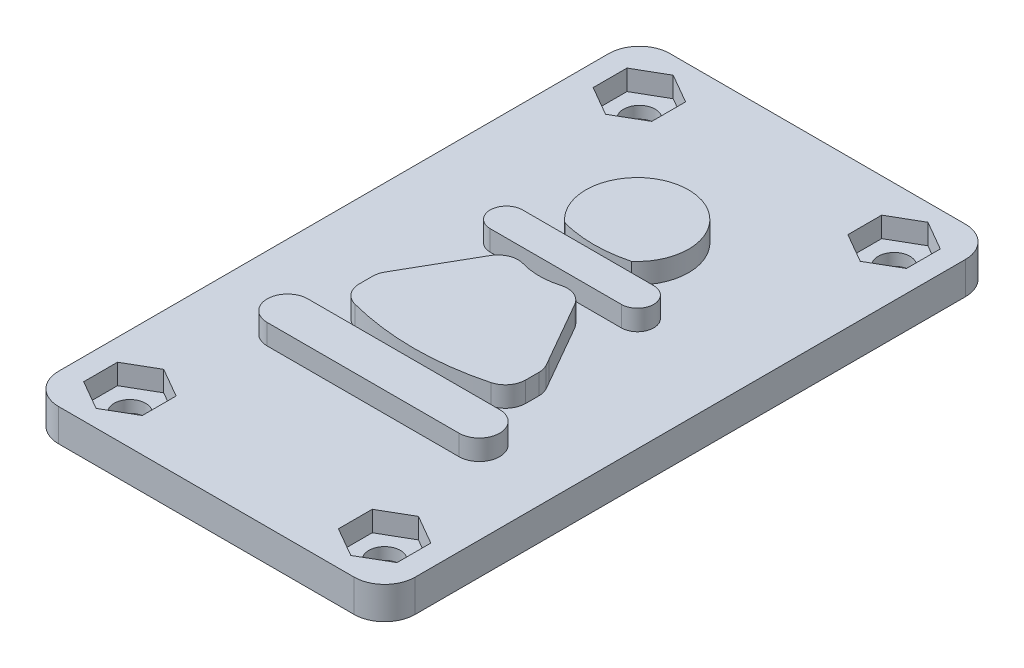
SolidWorks part; units mm, degrees
ref_plane "Front Plane" through (0, 0, 0) normal (0, 0, 1) x (1, 0, 0)
ref_plane "Top Plane" through (0, 0, 0) normal (0, 1, 0) x (1, 0, 0)
ref_plane "Right Plane" through (0, 0, 0) normal (1, 0, 0) x (0, 0, -1)
sketch "Sketch1" plane through (0, 0, 0) normal (0, 1, 0) x (1, 0, 0)
  line L1 (-12.5, -25) -> (12.5, -25) construction
  line L2 (-12.5, -25) -> (-12.5, 25) construction
  line L3 (-12.5, 25) -> (12.5, 25) construction
  line L4 (12.5, -25) -> (12.5, 25) construction
  line L5 (-12.5, -25) -> (12.5, 25) construction
  line L6 (-12.5, 25) -> (12.5, -25) construction
  line L7 (-17.5, -30) -> (17.5, -30)
  line L8 (-17.5, -30) -> (-17.5, 30)
  line L9 (-17.5, 30) -> (17.5, 30)
  line L10 (17.5, -30) -> (17.5, 30)
  line L11 (-17.5, -30) -> (17.5, 30) construction
  line L12 (-17.5, 30) -> (17.5, -30) construction
  line L13 (-12.5, 28.3198) -> (-15.375, 26.6599)
  line L14 (-15.375, 26.6599) -> (-15.375, 23.3401)
  line L15 (-15.375, 23.3401) -> (-12.5, 21.6802)
  line L16 (-12.5, 21.6802) -> (-9.625, 23.3401)
  line L17 (-9.625, 23.3401) -> (-9.625, 26.6599)
  line L18 (-9.625, 26.6599) -> (-12.5, 28.3198)
  line L19 (12.5, 28.3198) -> (9.625, 26.6599)
  line L20 (9.625, 26.6599) -> (9.625, 23.3401)
  line L21 (9.625, 23.3401) -> (12.5, 21.6802)
  line L22 (12.5, 21.6802) -> (15.375, 23.3401)
  line L23 (15.375, 23.3401) -> (15.375, 26.6599)
  line L24 (15.375, 26.6599) -> (12.5, 28.3198)
  line L25 (-12.5, -28.3198) -> (-9.625, -26.6599)
  line L26 (-9.625, -26.6599) -> (-9.625, -23.3401)
  line L27 (-9.625, -23.3401) -> (-12.5, -21.6802)
  line L28 (-12.5, -21.6802) -> (-15.375, -23.3401)
  line L29 (-15.375, -23.3401) -> (-15.375, -26.6599)
  line L30 (-15.375, -26.6599) -> (-12.5, -28.3198)
  line L31 (12.5, -21.6802) -> (9.625, -23.3401)
  line L32 (9.625, -23.3401) -> (9.625, -26.6599)
  line L33 (9.625, -26.6599) -> (12.5, -28.3198)
  line L34 (12.5, -28.3198) -> (15.375, -26.6599)
  line L35 (15.375, -26.6599) -> (15.375, -23.3401)
  line L36 (15.375, -23.3401) -> (12.5, -21.6802)
  circle A0 centre (-12.5, 25) radius 1.55
  circle A1 centre (12.5, 25) radius 1.55
  circle A2 centre (-12.5, -25) radius 1.55
  circle A3 centre (12.5, -25) radius 1.55
  circle A4 centre (-12.5, 25) radius 2.875 construction
  circle A5 centre (12.5, 25) radius 2.875 construction
  circle A6 centre (-12.5, -25) radius 2.875 construction
  circle A7 centre (12.5, -25) radius 2.875 construction
  point P0 (0, 0)
  point P10 (0, 0)
  dimension "D3" = 3.1
  dimension "D6" = 5.75
  dimension "D1" = 50
  dimension "D2" = 25
  dimension "D4" = 60
  dimension "D5" = 35
extrude "Boss-Extrude1" add sketch "Sketch1" along normal blind 3.175 contours L7 L10 L9 L8 L36 L35 L34 L33 L32 L31 L30 L29 L28 L27 L26 L25 L24 L23 L22 L21 L20 L19 L18 L17 L16 L15 L14 L13 | L17 L18 L13 L14 L15 L16 A0 | L23 L24 L19 L20 L21 L22 A1 | L35 L36 L31 L32 L33 L34 A3 | L29 L30 L25 L26 L27 L28 A2 region at (0, 0, 0) region at (-11.1064, 0, -27.4138) region at (13.8936, 0, -27.4138) region at (-13.8936, 0, 27.4138) region at (13.8936, 0, 22.5862)
extrude "Cut-Extrude1" cut sketch "Sketch1<3>" against normal blind 2 from surface contours L29 L30 L25 L26 L27 L28 A2 | L17 L18 L13 L14 L15 L16 A0 | L23 L24 L19 L20 L21 L22 A1 | L35 L36 L31 L32 L33 L34 A3 region at (-11.1064, 0, -27.4138) region at (13.8936, 0, -27.4138) region at (-13.8936, 0, 27.4138) region at (13.8936, 0, 22.5862) starting at face at (0, 3.175, 0)
sketch "Sketch1<3>" plane through (0, 0, 0) normal (0, 1, 0) x (1, 0, 0) same geometry as "Sketch1"
sketch "Sketch2" plane through (0, 3.175, 0) normal (0, 1, 0) x (1, 0, 0)
  line L3 (-3.2694, 3.5464) -> (-7.535, -3.8944)
  line L4 (7.535, -3.8944) -> (3.2694, 3.5464)
  line L5 (-3.2694, 3.5464) -> (3.2694, 3.5464) construction
  line L6 (-6.4344, 5.8874) -> (6.4344, 5.8874) construction
  line L7 (-6.4344, 7.4785) -> (6.4344, 7.4785)
  line L8 (-6.4344, 4.2964) -> (6.4344, 4.2964)
  line L9 (-8.1654, -5.0149) -> (-8.1654, -8.3102)
  line L10 (8.1654, -5.0149) -> (8.1654, -8.3102)
  line L11 (0, 3.5464) -> (0, -9.6177) construction
  line L12 (-9.4119, -12.6177) -> (9.4119, -12.6177) construction
  line L13 (-9.4119, -10.6177) -> (9.4119, -10.6177)
  line L14 (-9.4119, -14.6177) -> (9.4119, -14.6177)
  arc A0 (-3.2694, 8.4485) -> (3.2694, 8.4485) centre (0, 12.2891) cw
  arc A1 (-3.2694, 8.4485) -> (3.2694, 8.4485) centre (0, 20.8684) ccw
  arc A3 (-7.535, -3.8944) -> (-8.1654, -5.0149) centre (62.0717, -43.7978) ccw
  arc A5 (8.1654, -5.0149) -> (7.535, -3.8944) centre (-62.0717, -43.7978) ccw
  arc A6 (3.2694, 3.5464) -> (-3.2694, 3.5464) centre (0, 9.2494) cw
  arc A7 (-6.4344, 7.4785) -> (-6.4344, 4.2964) centre (-6.4344, 5.8874) ccw
  arc A8 (6.4344, 4.2964) -> (6.4344, 7.4785) centre (6.4344, 5.8874) ccw
  arc A9 (-8.1654, -8.3102) -> (8.1654, -8.3102) centre (0, 16.5321) ccw
  arc A10 (-9.4119, -10.6177) -> (-9.4119, -14.6177) centre (-9.4119, -12.6177) ccw
  arc A11 (9.4119, -14.6177) -> (9.4119, -10.6177) centre (9.4119, -12.6177) ccw
  point P7 (0, 5.8874)
  point P19 (0, 3.5464)
  point P25 (0, -12.6177)
  dimension "D1" = 0.75
  dimension "D2" = 1
  dimension "D3" = 4
extrude "Boss-Extrude2" add sketch "Sketch2" along normal blind 2 separate body
fillet "Fillet1" radius 2 6 edges at (8.1654, 4.175, 8.3102) (-8.1654, 4.175, 8.3102) (-8.1654, 4.175, 5.0149) (8.1654, 4.175, 5.0149) (3.2694, 4.175, -3.5464) (-3.2694, 4.175, -3.5464)
fillet "Fillet2" radius 3 4 edges at (-17.5, 1.5875, -30) (17.5, 1.5875, -30) (17.5, 1.5875, 30) (-17.5, 1.5875, 30)
